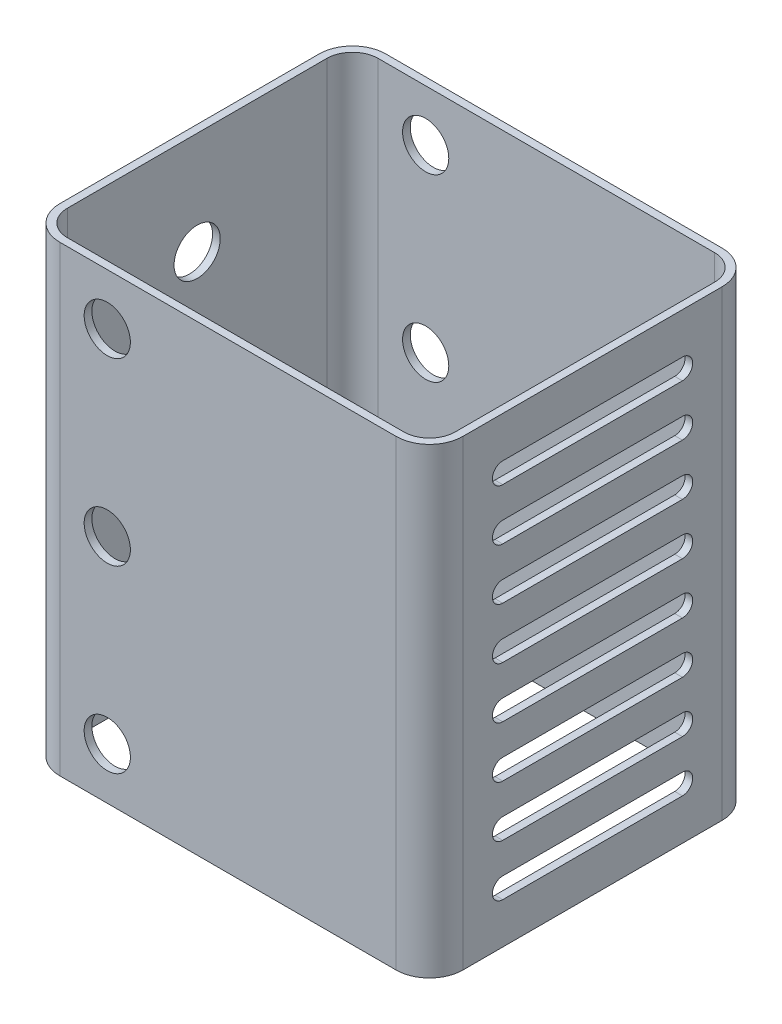
SolidWorks part; units mm, degrees
ref_plane "Front Plane" through (0, 0, 0) normal (0, 0, 1) x (1, 0, 0)
ref_plane "Top Plane" through (0, 0, 0) normal (0, 1, 0) x (1, 0, 0)
ref_plane "Right Plane" through (0, 0, 0) normal (1, 0, 0) x (0, 0, -1)
sketch "Sketch1" plane through (0, 0, 0) normal (0, 1, 0) x (1, 0, 0)
  line L0 (-32.75, -31.75) -> (32.75, -31.75)
  line L1 (-32.75, -30.25) -> (32.75, -30.25)
  line L2 (-37.75, -25.25) -> (-37.75, 25.25)
  line L3 (-32.75, 30.25) -> (32.75, 30.25)
  line L4 (37.75, -25.25) -> (37.75, 25.25)
  line L5 (-37.75, -30.25) -> (37.75, 30.25) construction
  line L6 (-37.75, 30.25) -> (37.75, -30.25) construction
  line L7 (39.25, -25.25) -> (39.25, 25.25)
  line L8 (-32.75, 31.75) -> (32.75, 31.75)
  line L9 (-39.25, -25.25) -> (-39.25, 25.25)
  arc A0 (32.75, 30.25) -> (37.75, 25.25) centre (32.75, 25.25) cw
  arc A1 (32.75, -30.25) -> (37.75, -25.25) centre (32.75, -25.25) ccw
  arc A2 (-32.75, -30.25) -> (-37.75, -25.25) centre (-32.75, -25.25) cw
  arc A3 (-37.75, 25.25) -> (-32.75, 30.25) centre (-32.75, 25.25) cw
  arc A4 (32.75, -31.75) -> (39.25, -25.25) centre (32.75, -25.25) ccw
  arc A5 (32.75, 31.75) -> (39.25, 25.25) centre (32.75, 25.25) cw
  arc A6 (-39.25, 25.25) -> (-32.75, 31.75) centre (-32.75, 25.25) cw
  arc A7 (-32.75, -31.75) -> (-39.25, -25.25) centre (-32.75, -25.25) cw
  point P0 (0, 0)
  dimension "D1" = 5
  dimension "D2" = 50.5
  dimension "D3" = 65.5
  dimension "D4" = 1.5
extrude "Boss-Extrude1" add sketch "Sketch1" along normal blind 90
sketch "Sketch2" plane through (-34.75, 0, 0) normal (-1, 0, 0) x (0, 0, 1)
  line L0 (0, 90) -> (0, 0) construction
  line L1 (-25.25, 90) -> (25.25, 90) construction
  line L2 (-25.25, 0) -> (25.25, 0) construction
  circle A0 centre (0, 70) radius 4.5
  circle A1 centre (0, 20) radius 4.5
  point P10 (0, 45)
  dimension "D1" = 9
  dimension "D2" = 9
  dimension "D3" = 50
  dimension "D4" = 25
extrude "Cut-Extrude1" cut sketch "Sketch2" along normal blind 17
sketch "Sketch3" plane through (0, 0, 32.25) normal (0, 0, 1) x (1, 0, 0)
  line L0 (-23.5, 90) -> (-23.5, 0) construction
  line L1 (-27.75, 90) -> (27.75, 90) construction
  line L2 (-27.75, 0) -> (27.75, 0) construction
  line L4 (-32.75, 90) -> (-32.75, 0) construction
  circle A0 centre (-23.5, 80) radius 4.5
  circle A1 centre (-23.5, 10) radius 4.5
  circle A2 centre (-23.5, 45) radius 4.5
  dimension "D2" = 9
  dimension "D1" = 9.25
  dimension "D3" = 70
  dimension "D4" = 35
extrude "Cut-Extrude2" cut sketch "Sketch3" against normal blind 95
sketch "Sketch4" plane through (34.75, 0, 0) normal (1, 0, 0) x (0, 0, -1)
  line L0 (-17.5, 80) -> (17.5, 80) construction
  line L1 (-17.5, 82) -> (17.5, 82)
  line L2 (-17.5, 78) -> (17.5, 78)
  line L3 (0, 80) -> (0, 90) construction
  line L4 (-25.25, 90) -> (25.25, 90) construction
  line L5 (-17.5, 70) -> (17.5, 70) construction
  line L6 (-17.5, 72) -> (17.5, 72)
  line L7 (-17.5, 68) -> (17.5, 68)
  line L8 (-17.5, 60) -> (17.5, 60) construction
  line L9 (-17.5, 62) -> (17.5, 62)
  line L10 (-17.5, 58) -> (17.5, 58)
  line L11 (-17.5, 50) -> (17.5, 50) construction
  line L12 (-17.5, 52) -> (17.5, 52)
  line L13 (-17.5, 48) -> (17.5, 48)
  line L14 (-17.5, 40) -> (17.5, 40) construction
  line L15 (-17.5, 42) -> (17.5, 42)
  line L16 (-17.5, 38) -> (17.5, 38)
  line L17 (-17.5, 30) -> (17.5, 30) construction
  line L18 (-17.5, 32) -> (17.5, 32)
  line L19 (-17.5, 28) -> (17.5, 28)
  line L20 (-17.5, 20) -> (17.5, 20) construction
  line L21 (-17.5, 22) -> (17.5, 22)
  line L22 (-17.5, 18) -> (17.5, 18)
  line L23 (-17.5, 10) -> (17.5, 10) construction
  line L24 (-17.5, 12) -> (17.5, 12)
  line L25 (-17.5, 8) -> (17.5, 8)
  arc A0 (-17.5, 82) -> (-17.5, 78) centre (-17.5, 80) ccw
  arc A1 (17.5, 78) -> (17.5, 82) centre (17.5, 80) ccw
  arc A2 (-17.5, 72) -> (-17.5, 68) centre (-17.5, 70) ccw
  arc A3 (17.5, 68) -> (17.5, 72) centre (17.5, 70) ccw
  arc A4 (-17.5, 62) -> (-17.5, 58) centre (-17.5, 60) ccw
  arc A5 (17.5, 58) -> (17.5, 62) centre (17.5, 60) ccw
  arc A6 (-17.5, 52) -> (-17.5, 48) centre (-17.5, 50) ccw
  arc A7 (17.5, 48) -> (17.5, 52) centre (17.5, 50) ccw
  arc A8 (-17.5, 42) -> (-17.5, 38) centre (-17.5, 40) ccw
  arc A9 (17.5, 38) -> (17.5, 42) centre (17.5, 40) ccw
  arc A10 (-17.5, 32) -> (-17.5, 28) centre (-17.5, 30) ccw
  arc A11 (17.5, 28) -> (17.5, 32) centre (17.5, 30) ccw
  arc A12 (-17.5, 22) -> (-17.5, 18) centre (-17.5, 20) ccw
  arc A13 (17.5, 18) -> (17.5, 22) centre (17.5, 20) ccw
  arc A14 (-17.5, 12) -> (-17.5, 8) centre (-17.5, 10) ccw
  arc A15 (17.5, 8) -> (17.5, 12) centre (17.5, 10) ccw
  point P2 (0, 80)
  point P15 (0, 70)
  point P22 (0, 60)
  point P29 (0, 50)
  point P36 (0, 40)
  point P43 (0, 30)
  point P50 (0, 20)
  point P57 (0, 10)
  dimension "D1" = 2
  dimension "D2" = 35
  dimension "D3" = 10
  dimension "D4" = 8
extrude "Cut-Extrude3" cut sketch "Sketch4" along normal blind 29
